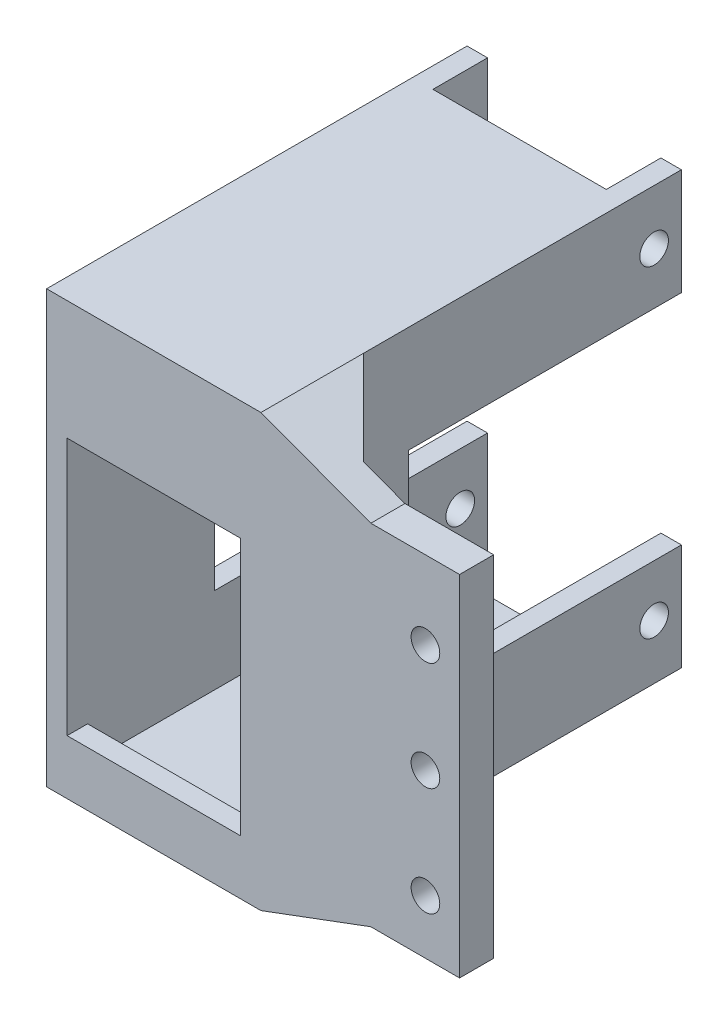
SolidWorks part; units mm, degrees
ref_plane "Front Plane" through (0, 0, 0) normal (1, 0, 0) x (0, 1, 0)
ref_plane "Top Plane" through (0, 0, 0) normal (0, 0, 1) x (0, 1, 0)
ref_plane "Right Plane" through (0, 0, 0) normal (0, 1, 0) x (-1, 0, 0)
sketch "Sketch1" plane through (0, 0, 0) normal (0, 0, 1) x (0, 1, 0)
  line L0 (-21.9, -15.7) -> (-15.9, -31.8)
  line L1 (-18.9, 12.7) -> (38.3, 12.7)
  line L2 (-18.9, 12.7) -> (-18.9, -12.7)
  line L3 (-18.9, -12.7) -> (38.3, -12.7)
  line L4 (38.3, 12.7) -> (38.3, -12.7)
  line L5 (-21.9, 15.7) -> (41.3, 15.7)
  line L6 (-21.9, 15.7) -> (-21.9, -15.7)
  line L7 (-21.9, -15.7) -> (41.3, -15.7)
  line L8 (41.3, 15.7) -> (41.3, -15.7)
  line L9 (-15.9, -31.8) -> (35.3, -31.8)
  line L10 (-15.9, -31.8) -> (-15.9, -44.8)
  line L11 (-15.9, -44.8) -> (35.3, -44.8)
  line L12 (35.3, -31.8) -> (35.3, -44.8)
  line L13 (41.3, -15.7) -> (35.3, -31.8)
  line L14 (23.85, 12.7) -> (23.85, -12.7)
  line L15 (-13.9, 12.7) -> (-13.9, -12.7)
  circle A0 centre (0, 0) radius 31.8
  circle A1 centre (-7.95, -39.8) radius 2.1
  circle A2 centre (7.95, -39.8) radius 2.1
  circle A3 centre (23.85, -39.8) radius 2.1
  dimension "D1" = 63.6
  dimension "D10" = 4.2
  dimension "D11" = 4.2
  dimension "D15" = 15.9
  dimension "D16" = 4.2
  dimension "D2" = 12.7
  dimension "D3" = 25.4
  dimension "D4" = 57.2
  dimension "D5" = 18.9
  dimension "D6" = 3
  dimension "D7" = 3
  dimension "D8" = 3
  dimension "D9" = 3
  dimension "D12" = 8
  dimension "D13" = 7.95
  dimension "D14" = 13
  dimension "D17" = 15.9
  dimension "D18" = 6
  dimension "D19" = 6
  dimension "D20" = 5
extrude "Boss-Extrude1" add sketch "Sketch1" against normal blind 3 contours A0 L9 L13 L7 | A0 L7 L0 | A0 L0 L9 | L12 L9 L10 L11 A3 A2 A1 | A0 L7 L8 L5 L1 L4 L3 | L7 A0 L3 L2 L1 L5 L6 | L3 A0 L1 | A0 L3 L4 L1 | L1 L2 L3 region at (22.4765, 1.4506, 0) region at (0, -21.3006, 0) region at (30.2052, -12.7473, 0) region at (14.3729, 28.7498, 0) region at (24.8393, 27.9696, 0) region at (38.2001, 9.8166, 0) region at (0, 34.5749, 0) region at (0, 27.435, 0) region at (0, -16.4, 0)
extrude "Boss-Extrude2" add sketch "Sketch1<4>" against normal blind 61.6 contours A0 L7 L8 L5 L1 L4 L3 | L7 A0 L3 L2 L1 L5 L6 region at (0, -21.3006, 0) region at (14.3729, 28.7498, 0)
sketch "Sketch1<4>" plane through (0, 0, 0) normal (0, 0, 1) x (0, 1, 0) same geometry as "Sketch1"
ref_plane "Plane1" through (-15.7, 0, 0) normal (-1, 0, 0) x (0, -1, 0)
sketch "Sketch2" plane through (-15.7, 0, 0) normal (-1, 0, 0) x (0, -1, 0)
  line L0 (21.9, -61.6) -> (-41.3, -61.6) construction
  line L1 (6.3, -61.6) -> (-25.7, -61.6)
  line L2 (6.3, -61.6) -> (6.3, -21.6)
  line L3 (6.3, -21.6) -> (-25.7, -21.6)
  line L4 (-25.7, -61.6) -> (-25.7, -21.6)
  circle A0 centre (13.9, -57.6) radius 2.1
  circle A1 centre (-33.3, -57.6) radius 2.1
  point P12 (-9.7, -61.6)
  dimension "D3" = 4.2
  dimension "D4" = 4.2
  dimension "D1" = 4
  dimension "D2" = 4
  dimension "D5" = 8
  dimension "D6" = 8
  dimension "D7" = 40
  dimension "D8" = 32
  dimension "D9" = 16
extrude "Cut-Extrude1" cut sketch "Sketch2" against normal blind 100
ref_plane "Plane2" through (0, 0, -61.6) normal (0, 0, -1) x (0, 1, 0)
sketch "Sketch3" plane through (0, 0, -61.6) normal (0, 0, -1) x (0, 1, 0)
  line L0 (25.7, 12.7) -> (-6.3, 12.7) construction
  line L1 (-21.9, 12.7) -> (41.3, 12.7)
  line L2 (-21.9, 12.7) -> (-21.9, -12.7)
  line L3 (-21.9, -12.7) -> (41.3, -12.7)
  line L4 (41.3, 12.7) -> (41.3, -12.7)
  line L5 (25.7, -12.7) -> (-6.3, -12.7) construction
  line L6 (41.3, -15.7) -> (41.3, 15.7) construction
  line L7 (-21.9, -15.7) -> (-21.9, 15.7) construction
extrude "Cut-Extrude2" cut sketch "Sketch3" against normal blind 8 contours L4 L1 L2 L3 region at (0, 9.7, -61.6)
extrude "Boss-Extrude3" add sketch "Sketch1<5>" against normal blind 5 contours A0 L7 L0 | A0 L9 L13 L7 | A0 L0 L9 | L12 L9 L10 L11 A3 A2 A1 region at (22.4765, 1.4506, 0) region at (30.2052, -12.7473, 0) region at (24.8393, 27.9696, 0) region at (38.2001, 9.8166, 0)
sketch "Sketch1<5>" plane through (0, 0, 0) normal (0, 0, 1) x (0, 1, 0) same geometry as "Sketch1"
chamfer "Chamfer1" distance 10 angle 45 1 edges at (15.7, 9.7, -5)
